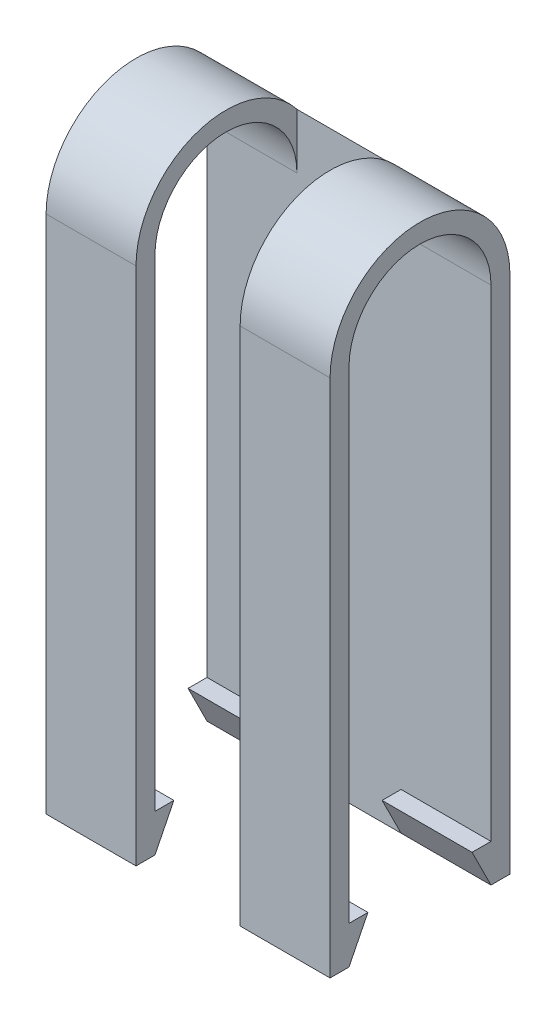
SolidWorks part; units mm, degrees
ref_plane "Front Plane" through (0, 0, 0) normal (0, 0, 1) x (1, 0, 0)
ref_plane "Top Plane" through (0, 0, 0) normal (0, 1, 0) x (1, 0, 0)
ref_plane "Right Plane" through (0, 0, 0) normal (1, 0, 0) x (0, 0, -1)
sketch "Sketch1" plane through (0, 0, 0) normal (1, 0, 0) x (0, 0, -1)
  line L0 (0, 0) -> (0, 54.9)
  line L1 (0, 54.9) -> (15, 54.9)
  line L2 (15, 54.9) -> (15, 0)
  line L3 (0, 0) -> (-2, 0)
  line L4 (-2, 0) -> (-2, 54.9)
  line L5 (15, 0) -> (17, 0)
  line L6 (17, 0) -> (17, 54.9)
  line L7 (15, 0) -> (13, 4)
  line L8 (13, 4) -> (15, 4)
  line L9 (7.5, 64.4) -> (7.5, -6.29) construction
  line L10 (0, 0) -> (2, 4)
  line L11 (2, 4) -> (0, 4)
  arc A0 (0, 54.9) -> (15, 54.9) centre (7.5, 54.9) cw
  arc A1 (-2, 54.9) -> (17, 54.9) centre (7.5, 54.9) cw
  point P11 (7.5, 64.4)
  dimension "D3" = 2
  dimension "D5" = 2
  dimension "D4" = 4
  dimension "D1" = 64.4
  dimension "D2" = 15
extrude "Boss-Extrude1" add sketch "Sketch1" against normal blind 30 contours A1 L4 L3 L0 A0 L2 L5 L6 | L9 A1 L4 L3 L0 A0 | L10 L11 L0 | L8 L7 L2 region at (0, 33.8834, 0.4006) region at (0, 2.6667, -0.6667) region at (0, 33.8834, -15.4006) region at (0, 2.6667, -14.3333)
sketch "Sketch2" plane through (0, 0, 2) normal (0, 0, 1) x (1, 0, 0)
  line L0 (-15, 64.4) -> (-15, 0) construction
  line L2 (-30, 0) -> (0, 0) construction
  line L3 (0, 64.4) -> (-30, 64.4) construction
  line L4 (-20.5, 64.4) -> (-20.5, 0)
  line L5 (-20.5, 64.4) -> (-9.5, 64.4)
  line L6 (-15, 64.4) -> (-15, 0)
  line L7 (-9.5, 0) -> (-20.5, 0)
  line L8 (-9.5, 64.4) -> (-9.5, 0)
  line M8 (0, 54.9) -> (-30, 54.9)
  line M10 (-30, 0) -> (0, 0)
  dimension "D1" = 5.5
extrude "Cut-Extrude1" cut sketch "Sketch2" against normal blind 17 contours L8 L6 M8 M10 | L6 L4 M8 M10 | L6 L5 L4 M8 | L8 L5 L6 M8 region at (-17.75, 59.65, 2) region at (-17.75, 27.45, 2) region at (-12.25, 59.65, 2) region at (-12.25, 27.45, 2)
